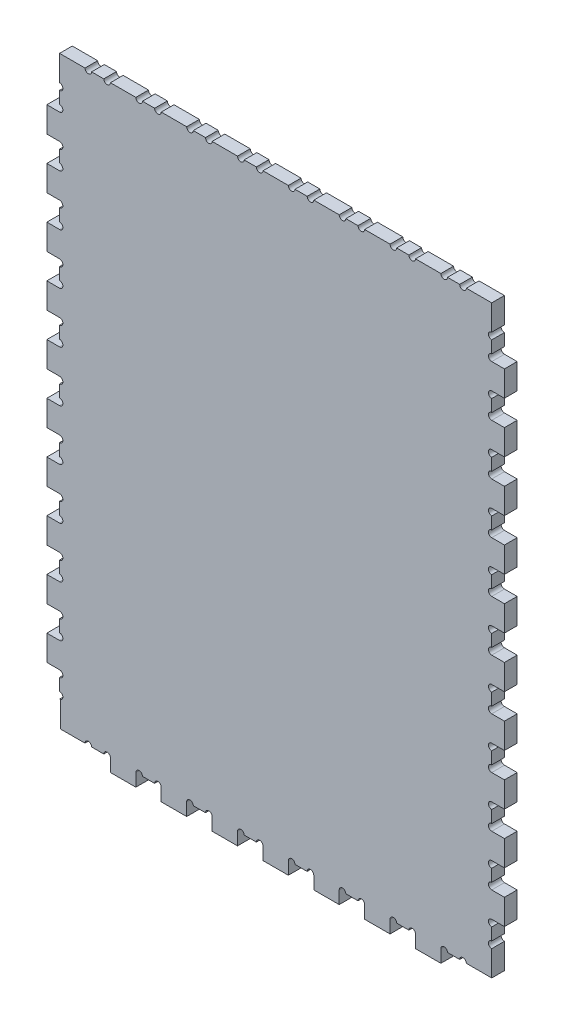
SolidWorks part; units mm, degrees
ref_plane "Front Plane" through (0, 0, 0) normal (0, 0, 1) x (1, 0, 0)
ref_plane "Top Plane" through (0, 0, 0) normal (0, 1, 0) x (1, 0, 0)
ref_plane "Right Plane" through (0, 0, 0) normal (1, 0, 0) x (0, 0, -1)
sketch "Sketch1" plane through (0, 0, 0) normal (0, 0, 1) x (1, 0, 0)
  line L1 (228.6, -304.8) -> (-228.6, -304.8)
  line L2 (228.6, -304.8) -> (228.6, 304.8)
  line L3 (228.6, 304.8) -> (-228.6, 304.8)
  line L4 (-228.6, -304.8) -> (-228.6, 304.8)
  line L5 (228.6, -304.8) -> (-228.6, 304.8) construction
  line L6 (228.6, 304.8) -> (-228.6, -304.8) construction
  line L9 (-203.2, 304.8) -> (-228.6, 304.8) construction
  point P0 (0, 0)
  dimension "D1" = 457.2
  dimension "D2" = 609.6
extrude "Boss-Extrude1" add sketch "Sketch1" along normal blind 12.7
sketch "Sketch2" plane through (0, 0, 12.7) normal (0, 0, 1) x (1, 0, 0)
  line L0 (228.6, 304.8) -> (-228.6, 304.8) construction
  line L1 (-190.5, 292.1) -> (-228.6, 292.1) construction
  line L2 (-190.5, 304.8) -> (-165.1, 304.8)
  line L3 (-190.5, 304.8) -> (-190.5, 292.1)
  line L4 (-190.5, 292.1) -> (-165.1, 292.1)
  line L5 (-165.1, 304.8) -> (-165.1, 292.1)
  line L6 (-228.6, 304.8) -> (-228.6, -304.8) construction
  circle A0 centre (-187.198, 292.1) radius 3.302
  circle A1 centre (-168.402, 292.1) radius 3.302
  line M10 (228.6, 304.8) -> (-228.6, 304.8)
  dimension "D4" = 6.604
  dimension "D5" = 6.604
  dimension "D1" = 25.4
  dimension "D2" = 12.7
  dimension "D3" = 38.1
extrude "Cut-Extrude1" cut sketch "Sketch2" against normal through all contours A1 L5 L3 A0 L4 M10 | L4 A0 | L4 A0 | L4 A1 | L4 A1 region at (-177.8, 299.0379, 12.7) region at (-187.198, 293.5014, 12.7) region at (-187.198, 290.6986, 12.7) region at (-168.402, 290.6986, 12.7) region at (-168.402, 293.5014, 12.7)
pattern_linear "LPattern1" count 8 spacing 50.8 along (1, 0, 0) of "Cut-Extrude1"
sketch "Sketch3" plane through (0, 0, 12.7) normal (0, 0, 1) x (1, 0, 0)
  line L0 (-228.6, 304.8) -> (-228.6, -304.8) construction
  line L1 (-228.6, 266.7) -> (-215.9, 266.7)
  line L2 (-228.6, 266.7) -> (-228.6, 241.3)
  line L3 (-228.6, 241.3) -> (-215.9, 241.3)
  line L4 (-215.9, 266.7) -> (-215.9, 241.3)
  line L5 (-215.9, 266.7) -> (-215.9, 304.8) construction
  line L7 (-190.5, 304.8) -> (-228.6, 304.8) construction
  circle A0 centre (-215.9, 263.398) radius 3.302
  circle A1 centre (-215.9, 244.602) radius 3.302
  dimension "D3" = 6.604
  dimension "D4" = 6.604
  dimension "D1" = 25.4
  dimension "D2" = 12.7
  dimension "D5" = 38.1
extrude "Cut-Extrude2" cut sketch "Sketch3" against normal through all contours A1 L4 A0 L1 L2 L3 | L4 A0 | L4 A1 | L4 A1 | L4 A0 region at (-222.8379, 254, 12.7) region at (-214.4986, 263.398, 12.7) region at (-217.3014, 263.398, 12.7) region at (-217.3014, 244.602, 12.7) region at (-214.4986, 244.602, 12.7)
pattern_linear "LPattern2" count 11 spacing 50.8 along (0, -1, 0) of "Cut-Extrude2"
ref_plane "Plane1" through (0, 0, 0) normal (1, 0, 0) x (0, 0, -1)
ref_plane "Plane2" through (0, 0, 0) normal (0, 1, 0) x (1, 0, 0)
mirror "Mirror1" about plane through (0, 0, 0) normal (1, 0, 0) of "LPattern2"
mirror "Mirror2" about plane through (0, 0, 0) normal (0, 1, 0) of "LPattern1"
sketch "Sketch4" plane through (0, 0, 12.7) normal (0, 0, 1) x (1, 0, 0)
  line L0 (-190.5, 304.8) -> (-228.6, 304.8) construction
  line L1 (-228.6, 266.7) -> (-215.9, 266.7)
  line L2 (-228.6, 266.7) -> (-228.6, 304.8)
  line L4 (-215.9, 266.7) -> (-215.9, 292.1)
  line L5 (-190.5, 304.8) -> (-190.5, 292.1) construction
  line L6 (-190.5, 304.8) -> (-228.6, 304.8)
  line L7 (-190.5, 304.8) -> (-190.5, 292.1)
  line L8 (-190.5, 292.1) -> (-215.9, 292.1)
  line L10 (228.6, 266.7) -> (228.6, 304.8) construction
  line L11 (-228.6, -304.8) -> (-190.5, -304.8)
  line L12 (-228.6, -304.8) -> (-228.6, -292.1)
  line L13 (-214.7522, -292.1) -> (-190.5, -292.1)
  line L14 (-190.5, -304.8) -> (-190.5, -292.1)
  line L15 (-228.6, -266.7) -> (-214.7522, -266.7)
  line L16 (-228.6, -266.7) -> (-228.6, -304.8)
  line L17 (-228.6, -304.8) -> (-214.7522, -304.8)
  line L18 (-214.7522, -266.7) -> (-214.7522, -292.1)
  line L19 (228.6, -304.8) -> (190.5, -304.8)
  line L20 (228.6, -304.8) -> (228.6, -292.1)
  line L21 (215.9, -292.1) -> (190.5, -292.1)
  line L22 (190.5, -304.8) -> (190.5, -292.1)
  line L23 (228.6, -266.7) -> (215.9, -266.7)
  line L24 (228.6, -266.7) -> (228.6, -304.8)
  line L25 (228.6, -304.8) -> (215.9, -304.8)
  line L26 (215.9, -266.7) -> (215.9, -292.1)
  line L27 (190.5, 304.8) -> (228.6, 304.8)
  line L28 (190.5, 304.8) -> (190.5, 292.1)
  line L29 (190.5, 292.1) -> (215.9, 292.1)
  line L30 (228.6, 304.8) -> (228.6, 292.1)
  line L32 (228.6, 266.7) -> (215.9, 266.7)
  line L33 (228.6, 266.7) -> (228.6, 304.8)
  line L34 (228.6, 304.8) -> (215.9, 304.8)
  line L35 (215.9, 266.7) -> (215.9, 292.1)
  arc A0 (-183.896, -292.1) -> (-190.5, -292.1) centre (-187.198, -292.1) ccw construction
extrude "Cut-Extrude3" cut sketch "Sketch4" against normal through all contours L18 L15 L16 L12 L11 L14 L13 | L23 L26 L21 L22 L19 L20 L24 | L35 L32 L33 L30 L27 L28 L29 | L8 L7 L6 L2 L1 L4 region at (-228.0612, 285.75, 12.7) region at (-228.0612, -298.45, 12.7) region at (222.25, -304.2612, 12.7) region at (203.2, 304.2612, 12.7)
sketch "Sketch5" plane through (0, 0, 12.7) normal (0, 0, 1) x (1, 0, 0)
  line L0 (-215.9, 266.7) -> (-215.9, 292.1) construction
  line L1 (-215.9, 292.1) -> (215.9, 292.1)
  line L2 (-215.9, 292.1) -> (-215.9, 304.8732)
  line L3 (-215.9, 304.8732) -> (215.9, 304.8732)
  line L4 (215.9, 292.1) -> (215.9, 304.8732)
extrude "Cut-Extrude4" cut sketch "Sketch5" against normal through all
